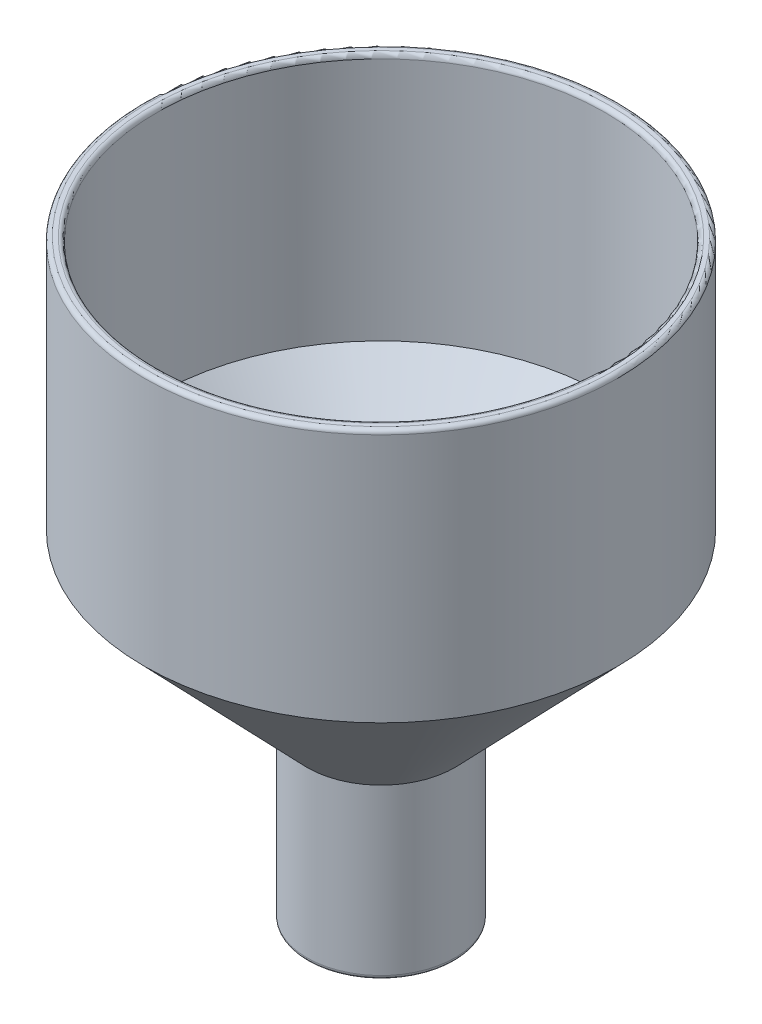
SolidWorks part; units mm, degrees
ref_plane "Front Plane" through (0, 0, 0) normal (0, 0, 1) x (1, 0, 0)
ref_plane "Top Plane" through (0, 0, 0) normal (0, 1, 0) x (1, 0, 0)
ref_plane "Right Plane" through (0, 0, 0) normal (1, 0, 0) x (0, 0, -1)
ref_axis "Axis1" through (0, 0, 0) along (0, 1, 0)
sketch "Sketch1" plane through (0, 0, 0) normal (0, 0, 1) x (1, 0, 0)
  line L0 (-7.25, 0.0833) -> (-7.25, 20.6879)
  line L1 (-7.25, 20.6879) -> (-26.5, 40.6879)
  line L2 (-26.5, 40.6879) -> (-26.5, 70.0833)
  line L3 (-26.5, 70.0833) -> (-28, 70.0833)
  line L4 (-28, 70.0833) -> (-28, 40.0833)
  line L5 (-28, 40.0833) -> (-8.75, 20.0833)
  line L6 (-8.75, 20.0833) -> (-8.75, 0.0833)
  line L7 (-8.75, 0.0833) -> (-7.25, 0.0833)
  dimension "D1" = 26.5
  dimension "D2" = 7.25
  dimension "D3" = 1.5
  dimension "D4" = 1.5
  dimension "D5" = 1.5
  dimension "D6" = 20
  dimension "D7" = 30
  dimension "D8" = 20
revolve "Revolve1" add sketch "Sketch1" angle 360 about axis through (0, 0, 0) along (0, 1, 0)
fillet "Fillet1" radius 0.5 4 edges at (0, 70.0833, -26.5) (0, 70.0833, -28) (0, 0.0833, -7.25) (0, 0.0833, -8.75)
